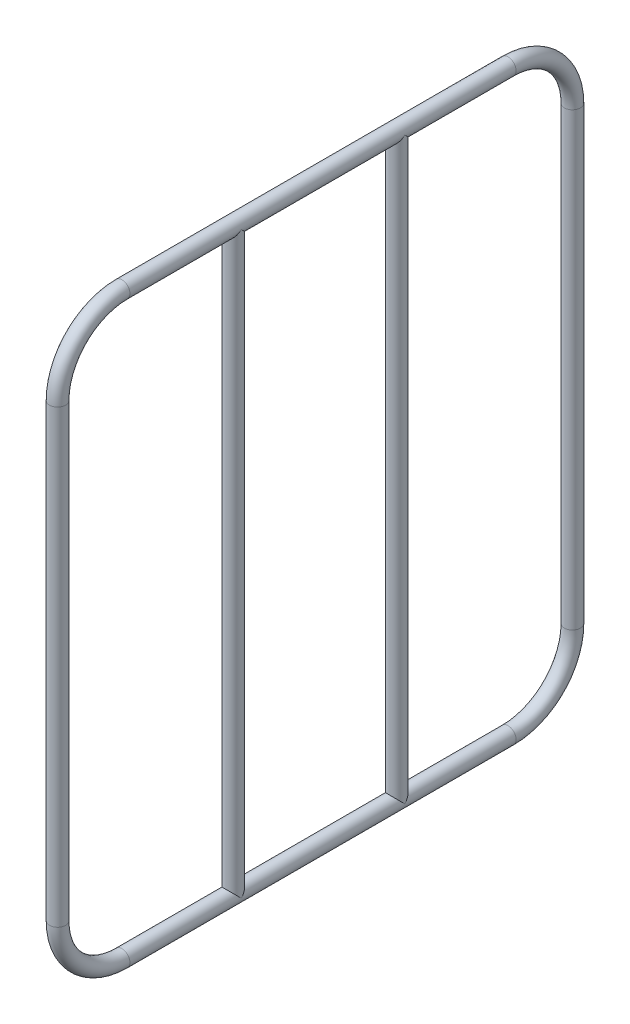
SolidWorks part; units mm, degrees
ref_plane "Front Plane" through (0, 0, 0) normal (0, 0, 1) x (1, 0, 0)
ref_plane "Top Plane" through (0, 0, 0) normal (0, 1, 0) x (1, 0, 0)
ref_plane "Right Plane" through (0, 0, 0) normal (1, 0, 0) x (0, 0, -1)
sketch "Sketch1" plane through (0, 0, 0) normal (1, 0, 0) x (0, 0, -1)
  line L0 (-400, 800) -> (-400, 100)
  line L1 (-300, 900) -> (300, 900)
  line L2 (400, 800) -> (400, 100)
  line L5 (-300, 0) -> (300, 0)
  arc A0 (-400, 800) -> (-300, 900) centre (-300, 800) cw
  arc A1 (300, 900) -> (400, 800) centre (300, 800) cw
  arc A2 (400, 100) -> (300, 0) centre (300, 100) cw
  arc A3 (-300, 0) -> (-400, 100) centre (-300, 100) cw
  point P14 (0, 0)
  dimension "D1" = 100
  dimension "D4" = 100
  dimension "D2" = 900
  dimension "D3" = 800
sweep "Sweep-Thin1" add path "Sketch1" circular profile diameter 25 parameters "D1"=2, "D3"=25
sketch "Sketch27" plane through (0, 0, 0) normal (1, 0, 0) x (0, 0, -1)
  line L0 (-300, 900) -> (300, 900) construction
  line L1 (-127, 900) -> (127, 900)
  line L2 (-127, 900) -> (-127, 0)
  line L3 (-127, 0) -> (127, 0)
  line L4 (127, 900) -> (127, 0)
  line L5 (-300, 0) -> (300, 0) construction
  dimension "D1" = 254
  dimension "D2" = 127
sweep "Sweep-Thin3" add path "Sketch27" circular profile diameter 25 parameters "D1"=2, "D3"=25
